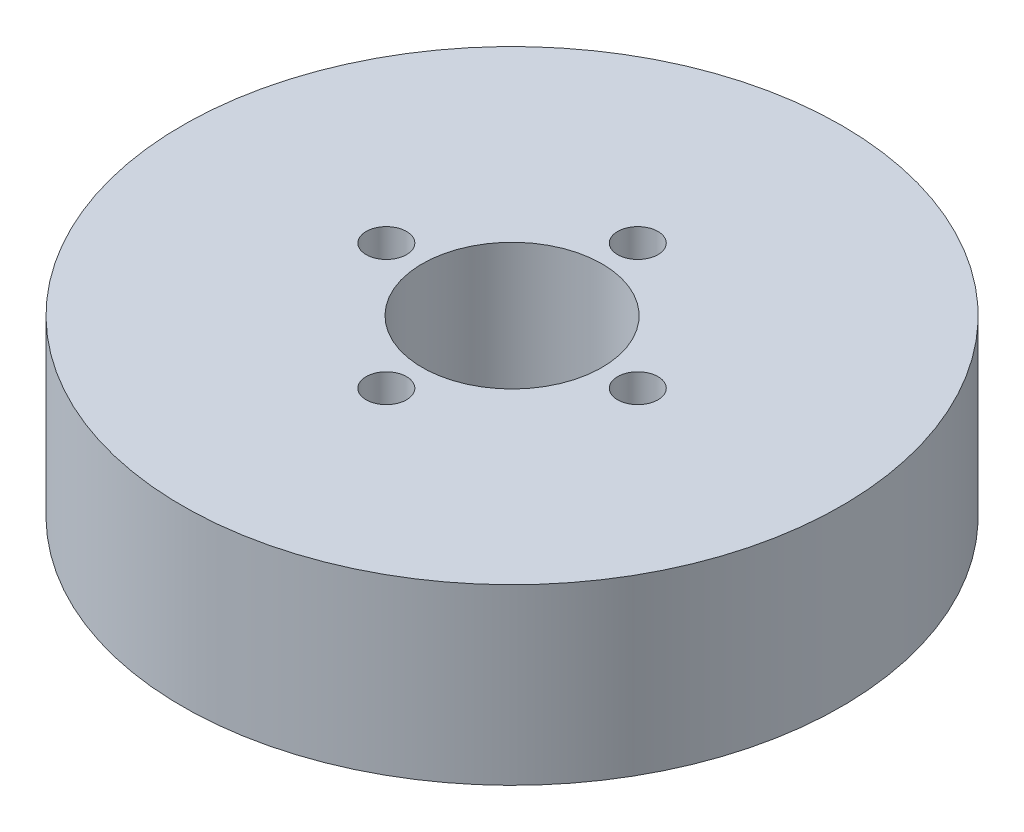
SolidWorks part; units mm, degrees
ref_plane "Front Plane" through (0, 0, 0) normal (0, 0, 1) x (1, 0, 0)
ref_plane "Top Plane" through (0, 0, 0) normal (0, 1, 0) x (1, 0, 0)
ref_plane "Right Plane" through (0, 0, 0) normal (1, 0, 0) x (0, 0, -1)
sketch "Sketch1" plane through (0, 0, 0) normal (0, 1, 0) x (1, 0, 0)
  circle A0 centre (0, 0) radius 55
  dimension "FLANGE_OD" = 110
extrude "Boss-Extrude1" add sketch "Sketch1" along normal blind 29
sketch "Sketch2" plane through (0, 0, 0) normal (0, 1, 0) x (1, 0, 0)
  circle A0 centre (0, 0) radius 15
  dimension "BORE_D" = 30
extrude "Cut-Extrude1" cut sketch "Sketch2" along normal through all
sketch "Sketch3" plane through (0, 29, 0) normal (0, 1, 0) x (1, 0, 0)
  circle A0 centre (0, 0) radius 20.9811 construction
  circle A1 centre (-20.9811, 0) radius 3.3661
  dimension "BOLT_D" = 6.7323
  dimension "BOLT_PCD" = 41.9622
extrude "Cut-Extrude2" cut sketch "Sketch3" against normal blind 19.2425
pattern_circular "CirPattern1" count 4 over 360 about axis through (0, 0, 0) along (0, 1, 0) of "Cut-Extrude2"
